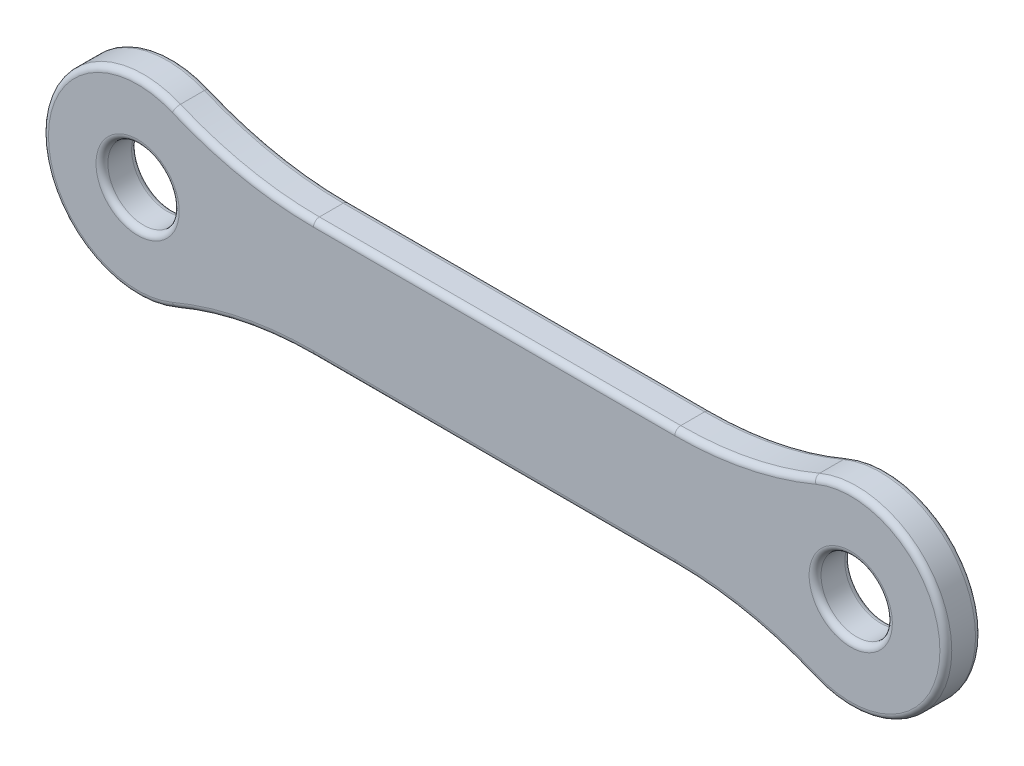
SolidWorks part; units mm, degrees
material "AR-M2"
ref_plane "正面" through (0, 0, 0) normal (0, 0, 1) x (1, 0, 0)
ref_plane "平面" through (0, 0, 0) normal (0, 1, 0) x (1, 0, 0)
ref_plane "右側面" through (0, 0, 0) normal (1, 0, 0) x (0, 0, -1)
sketch "ｽｹｯﾁ1" plane through (0, 0, 0) normal (0, 0, 1) x (1, 0, 0)
  line L0 (0, 0) -> (60, 0) construction
  line L1 (0, 5) -> (60, 5)
  line L2 (60, -5) -> (0, -5)
  arc A0 (0, 5) -> (0, -5) centre (0, 0) ccw
  arc A1 (60, -5) -> (60, 5) centre (60, 0) ccw
  circle A2 centre (0, 0) radius 3
  circle A3 centre (60, 0) radius 3
  dimension "D2" = 10
  dimension "D3" = 10
  dimension "D4" = 6
  dimension "D1" = 60
extrude "ﾎﾞｽ - 押し出し1" add sketch "ｽｹｯﾁ1" along normal blind 3
sketch "ｽｹｯﾁ2" plane through (0, 0, 0) normal (0, 0, -1) x (-1, 0, 0)
  circle A0 centre (0, 0) radius 3
  dimension "D1" = 6
extrude "ｶｯﾄ - 押し出し1" [suppressed] cut sketch "ｽｹｯﾁ2" against normal through all
sketch "ｽｹｯﾁ3" plane through (0, 0, 3) normal (0, 0, 1) x (1, 0, 0)
  line L0 (30, 5) -> (30, -5) construction
  line L1 (60, 5) -> (0, 5) construction
  line L2 (0, -5) -> (60, -5) construction
  circle A0 centre (0, 0) radius 8
  circle A1 centre (0, 0) radius 3 construction
  circle A2 centre (0, 0) radius 3
  circle A3 centre (60, 0) radius 3
  circle A4 centre (60, 0) radius 8
  dimension "D1" = 5
  dimension "D2" = 16
extrude "ﾎﾞｽ - 押し出し2" add sketch "ｽｹｯﾁ3" against normal up to surface (3 mm away) up to face at (30, 0, 0)
fillet "ﾌｨﾚｯﾄ2" radius 30 4 edges at (6.245, -5, 1.5) (53.755, -5, 1.5) (53.755, 5, 1.5) (6.245, 5, 1.5)
fillet "ﾌｨﾚｯﾄ1" radius 0.5 20 edges at (63, 0, 0) (30, -5, 0) (30, 5, 0) (3, 0, 0) (63, 0, 3) (30, 5, 3) (30, -5, 3) (3, 0, 3) (8.8383, 5.5981, 0) (-8, 0, 0) (8.8383, -5.5981, 0) (51.1617, -5.5981, 0) (68, 0, 0) (51.1617, 5.5981, 0) (8.8383, 5.5981, 3) (51.1617, 5.5981, 3) (68, 0, 3) (51.1617, -5.5981, 3) (8.8383, -5.5981, 3) (-8, 0, 3)
